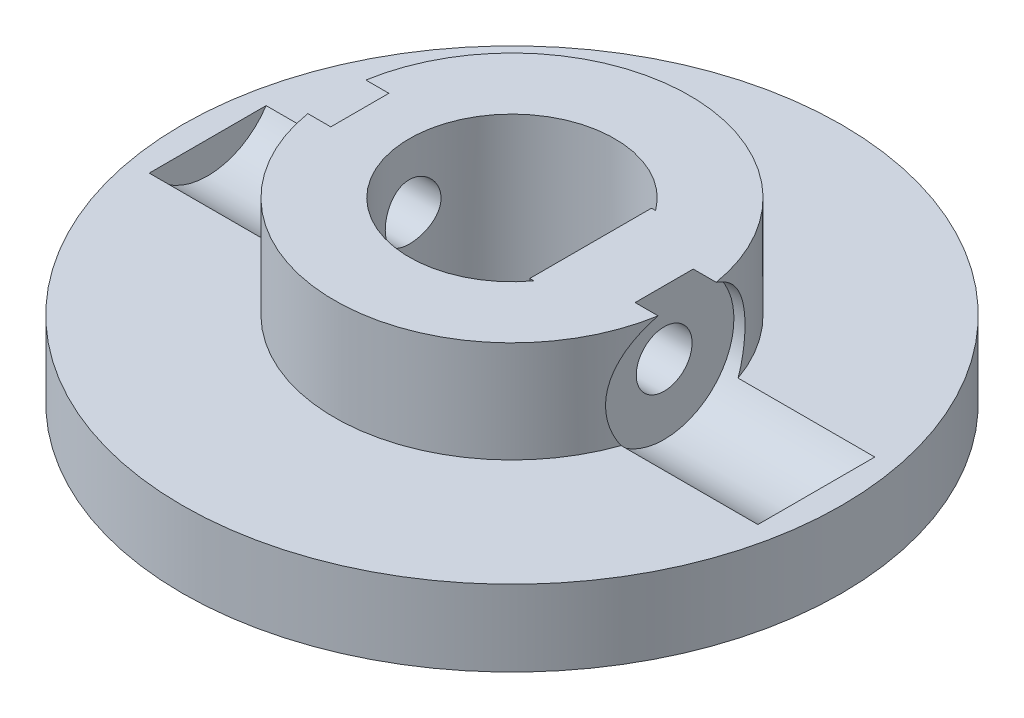
SolidWorks part; units mm, degrees
ref_plane "Front Plane" through (0, 0, 0) normal (0, 0, 1) x (1, 0, 0)
ref_plane "Top Plane" through (0, 0, 0) normal (0, 1, 0) x (1, 0, 0)
ref_plane "Right Plane" through (0, 0, 0) normal (1, 0, 0) x (0, 0, -1)
sketch "Stock_horn_drive_flange_profile" plane through (0, 0, 0) normal (0, 1, 0) x (1, 0, 0)
  circle A0 centre (0, 0) radius 13
  circle A1 centre (0, 0) radius 4.05
  dimension "D1" = 26
  dimension "D2" = 8.1
extrude "Stock_horn_drive_flange" add sketch "Stock_horn_drive_flange_profile" along normal blind 3 from offset 41
sketch "D_coupling_ring_profile" plane through (0, 0, 0) normal (0, 1, 0) x (1, 0, 0)
  circle A0 centre (0, 0) radius 7
  circle A1 centre (0, 0) radius 4.05
  dimension "D1" = 14
  dimension "D2" = 8.1
extrude "D_coupling_ring" add sketch "D_coupling_ring_profile" along normal blind 4 from offset 44
sketch "D_key_land_profile" plane through (0, 0, 0) normal (0, 1, 0) x (1, 0, 0)
  line L1 (3.1, -2.4) -> (6, -2.4)
  line L2 (3.1, -2.4) -> (3.1, 2.4)
  line L3 (3.1, 2.4) -> (6, 2.4)
  line L4 (6, -2.4) -> (6, 2.4)
  dimension "D1" = 2.9
  dimension "D2" = 4.8
  dimension "D3" = 3.1
  dimension "D4" = 2.4
extrude "D_key_land" add sketch "D_key_land_profile" along normal blind 4 from offset 44
sketch "Captured_horn_key_boss_profile" plane through (0, 0, 0) normal (0, 1, 0) x (1, 0, 0)
  circle A0 centre (0, 0) radius 13
  dimension "D1" = 26
extrude "Captured_horn_key_boss_SUPERSEDED_owned_servo" [suppressed] add sketch "Captured_horn_key_boss_profile" along normal blind 1.65 from offset 39.35
sketch "Stock_horn_pocket_Hub" plane through (0, 0, 0) normal (0, 1, 0) x (1, 0, 0)
  circle A0 centre (0, 0) radius 3.55
  dimension "D1" = 7.1
extrude "Key_pocket_Hub_SUPERSEDED_owned_servo" [suppressed] cut sketch "Stock_horn_pocket_Hub" along normal blind 1.65 from offset 39.35
sketch "Stock_horn_pocket_Horizontal" plane through (0, 0, 0) normal (0, 1, 0) x (1, 0, 0)
  line L1 (-8.15, -2.1) -> (8.15, -2.1)
  line L2 (-8.15, -2.1) -> (-8.15, 2.1)
  line L3 (-8.15, 2.1) -> (8.15, 2.1)
  line L4 (8.15, -2.1) -> (8.15, 2.1)
  dimension "D1" = 16.3
  dimension "D2" = 4.2
  dimension "D3" = 8.15
  dimension "D4" = 2.1
extrude "Key_pocket_Horizontal_SUPERSEDED_owned_servo" [suppressed] cut sketch "Stock_horn_pocket_Horizontal" along normal blind 1.65 from offset 39.35
sketch "Stock_horn_pocket_Vertical" plane through (0, 0, 0) normal (0, 1, 0) x (1, 0, 0)
  line L1 (-2.1, -8.15) -> (2.1, -8.15)
  line L2 (-2.1, -8.15) -> (-2.1, 8.15)
  line L3 (-2.1, 8.15) -> (2.1, 8.15)
  line L4 (2.1, -8.15) -> (2.1, 8.15)
  dimension "D1" = 4.2
  dimension "D2" = 16.3
  dimension "D3" = 2.1
  dimension "D4" = 8.15
extrude "Key_pocket_Vertical_SUPERSEDED_owned_servo" [suppressed] cut sketch "Stock_horn_pocket_Vertical" along normal blind 1.65 from offset 39.35
sketch "Stock_horn_pocket_Rounded_tips" plane through (0, 0, 0) normal (0, 1, 0) x (1, 0, 0)
  circle A0 centre (8.15, 0) radius 2.1
  circle A1 centre (-8.15, 0) radius 2.1
  circle A2 centre (0, 8.15) radius 2.1
  circle A3 centre (0, -8.15) radius 2.1
  dimension "D1" = 4.2
  dimension "D2" = 4.2
  dimension "D3" = 4.2
  dimension "D4" = 4.2
  dimension "D5" = 8.15
  dimension "D6" = 8.15
  dimension "D7" = 8.15
  dimension "D8" = 8.15
extrude "Key_pocket_Rounded_tips_SUPERSEDED_owned_servo" [suppressed] cut sketch "Stock_horn_pocket_Rounded_tips" along normal blind 1.65 from offset 39.35
sketch "Unmodified_horn_capture_M2_profile" plane through (0, 0, 0) normal (0, 1, 0) x (1, 0, 0)
  circle A0 centre (7, 7) radius 1.15
  circle A1 centre (-7, 7) radius 1.15
  circle A2 centre (-7, -7) radius 1.15
  circle A3 centre (7, -7) radius 1.15
  dimension "D1" = 2.3
  dimension "D2" = 2.3
  dimension "D3" = 2.3
  dimension "D4" = 2.3
  dimension "D5" = 7
  dimension "D6" = 7
  dimension "D7" = 7
  dimension "D8" = 7
extrude "Unmodified_horn_capture_M2_SUPERSEDED_owned_servo" [suppressed] cut sketch "Unmodified_horn_capture_M2_profile" along normal through all from offset 50 offset against normal yes
sketch "Horn_center_hub_clearance" plane through (0, 0, 0) normal (0, 1, 0) x (1, 0, 0)
  circle A0 centre (0, 0) radius 4
  dimension "D1" = 8
extrude "Hub_clearance_in_key_boss_only_SUPERSEDED_owned_servo" [suppressed] cut sketch "Horn_center_hub_clearance" along normal blind 1.65 from offset 39.35
sketch "Yaw_positive_retention_crossbolt_profile" plane through (0, 0, 0) normal (1, 0, 0) x (0, 0, -1)
  circle A0 centre (0, 45.5) radius 1.1
  dimension "D1" = 2.2
  dimension "D2" = 45.5
extrude "Yaw_positive_retention_crossbolt" cut sketch "Yaw_positive_retention_crossbolt_profile" along normal through all from offset 10 offset against normal yes
sketch "Crossbolt_flat_seat_-12" plane through (0, 0, 0) normal (1, 0, 0) x (0, 0, -1)
  circle A0 centre (0, 45.5) radius 2.75
  dimension "D1" = 5.5
  dimension "D2" = 45.5
extrude "Crossbolt_flat_seat_cut_-12" cut sketch "Crossbolt_flat_seat_-12" along normal blind 6 from offset 12 offset against normal yes
sketch "Crossbolt_flat_seat_6" plane through (0, 0, 0) normal (1, 0, 0) x (0, 0, -1)
  circle A0 centre (0, 45.5) radius 2.75
  dimension "D1" = 5.5
  dimension "D2" = 45.5
extrude "Crossbolt_flat_seat_cut_6" cut sketch "Crossbolt_flat_seat_6" along normal blind 6 from offset 6
sketch "SG90_spline_socket_boss_profile" plane through (0, 0, 0) normal (0, 1, 0) x (1, 0, 0)
  circle A0 centre (0, 0) radius 6
  dimension "D1" = 12
extrude "SG90_spline_socket_boss_OD12" add sketch "SG90_spline_socket_boss_profile" along normal blind 3.7 from offset 37.3
sketch "SG90_spline_press_socket_D4p85_depth2p5_profile" plane through (0, 0, 0) normal (0, 1, 0) x (1, 0, 0)
  circle A0 centre (0, 0) radius 2.425
  dimension "D1" = 4.85
extrude "SG90_spline_press_socket_D4p85_depth2p5" cut sketch "SG90_spline_press_socket_D4p85_depth2p5_profile" along normal blind 2.5 from offset 37.3
sketch "SG90_centre_screw_clearance_D2p4_profile" plane through (0, 0, 0) normal (0, 1, 0) x (1, 0, 0)
  circle A0 centre (0, 0) radius 1.2
  dimension "D1" = 2.4
extrude "SG90_centre_screw_clearance_D2p4" cut sketch "SG90_centre_screw_clearance_D2p4_profile" along normal blind 1.2 from offset 39.8
